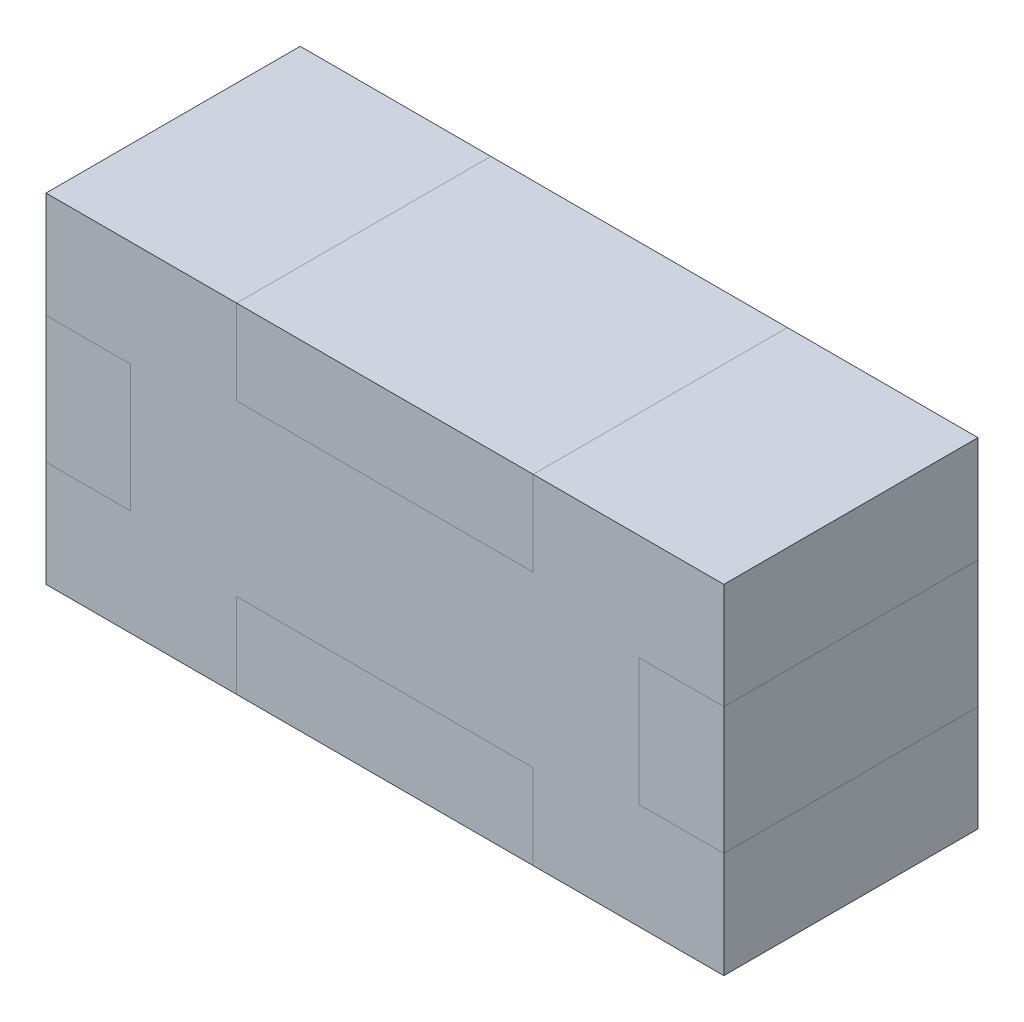
SolidWorks part; units mm, degrees
note: The reader was unsure of these and kept them because the rebuilt part matched: shared geometry of "Sketch2<4>".
ref_plane "Front Plane" through (0, 0, 0) normal (0, 0, 1) x (1, 0, 0)
ref_plane "Top Plane" through (0, 0, 0) normal (0, 1, 0) x (1, 0, 0)
ref_plane "Right Plane" through (0, 0, 0) normal (1, 0, 0) x (0, 0, -1)
sketch "Sketch1" plane through (0, 0, 0) normal (0, 0, 1) x (1, 0, 0)
  line L1 (-0.8, 0.4) -> (0.8, 0.4)
  line L2 (-0.8, 0.4) -> (-0.8, -0.4)
  line L3 (-0.8, -0.4) -> (0.8, -0.4)
  line L4 (0.8, 0.4) -> (0.8, -0.4)
  line L5 (-0.8, 0.4) -> (0.8, -0.4) construction
  line L6 (-0.8, -0.4) -> (0.8, 0.4) construction
  point P0 (0, 0)
  dimension "D1" = 1.6
  dimension "D2" = 0.8
extrude "Boss-Extrude1" add sketch "Sketch1" along normal blind 0.6 contours L1 L4 L3 L2
sketch "Sketch2" plane through (0, 0, 0.6) normal (0, 0, 1) x (1, 0, 0)
  line L0 (-0.8, -0.4) -> (0.8, -0.4) construction
  line L1 (-0.35, -0.4) -> (0.35, -0.4)
  line L2 (-0.35, -0.4) -> (-0.35, -0.1999)
  line L3 (-0.35, -0.1999) -> (0.35, -0.1999)
  line L4 (0.35, -0.4) -> (0.35, -0.1999)
  line L5 (-0.8, 0.4) -> (-0.8, -0.4) construction
  line L6 (-0.8, 0.15) -> (-0.6, 0.15)
  line L7 (-0.8, 0.15) -> (-0.8, -0.15)
  line L8 (-0.8, -0.15) -> (-0.6, -0.15)
  line L9 (-0.6, 0.15) -> (-0.6, -0.15)
  line L10 (-0.8, 0.4) -> (0.8, 0.4) construction
  line L11 (0.33, 0) -> (-0.33, 0) construction
  line L12 (0.35, 0.4) -> (0.35, 0.1999)
  line L13 (-0.35, 0.4) -> (-0.35, 0.1999)
  line L14 (-0.35, 0.1999) -> (0.35, 0.1999)
  line L15 (-0.35, 0.4) -> (0.35, 0.4)
  line L16 (0, -0.33) -> (0, 0.33) construction
  line L17 (0.6, 0.15) -> (0.6, -0.15)
  line L18 (0.8, -0.15) -> (0.6, -0.15)
  line L19 (0.8, 0.15) -> (0.8, -0.15)
  line L20 (0.8, 0.15) -> (0.6, 0.15)
  point P14 (0, 0)
  dimension "D1" = 0.7
  dimension "D2" = 0.2001
  dimension "D3" = 0.45
  dimension "D4" = 0.2
  dimension "D5" = 0.25
  dimension "D6" = 0.3
extrude "Cut-Extrude1" cut sketch "Sketch2" against normal blind 0.6 contours L14 L12 L15 L13
extrude "Boss-Extrude2" add sketch "Sketch2<4>" against normal blind 0.6 separate body contours L1 L4 L3 L2
sketch "Sketch2<4>" plane through (0, 0, 0.6) normal (0, 0, 1) x (1, 0, 0) same geometry as "Sketch2"
